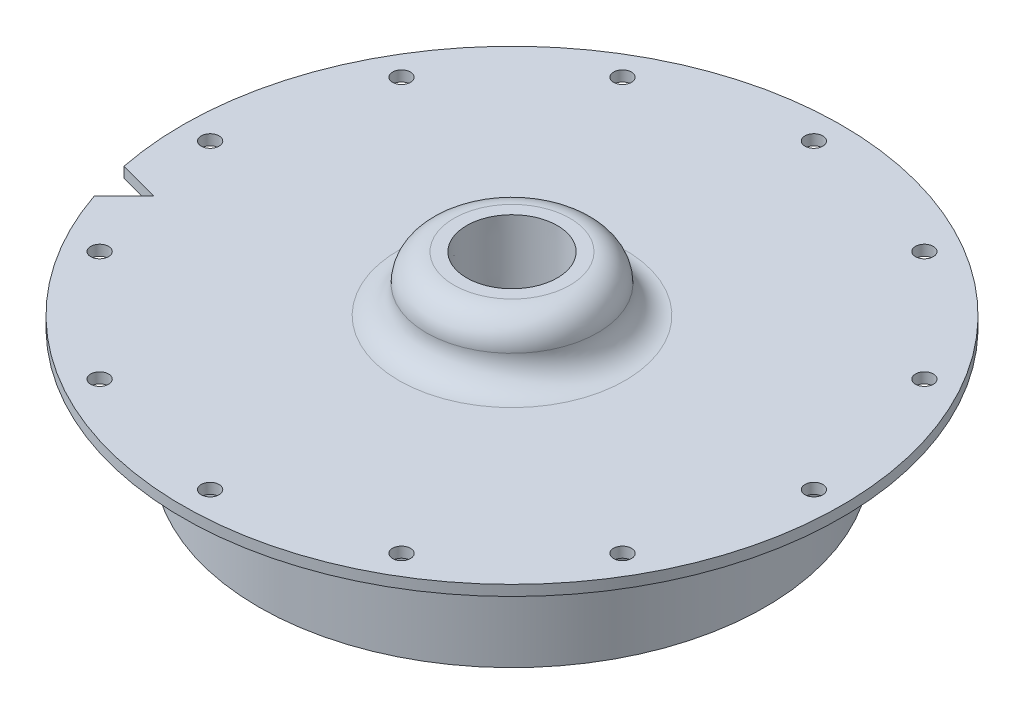
SolidWorks part; units mm, degrees
material "6063-T6"
ref_plane "Front Plane" through (0, 0, 0) normal (0, 0, 1) x (1, 0, 0)
ref_plane "Top Plane" through (0, 0, 0) normal (0, 1, 0) x (1, 0, 0)
ref_plane "Right Plane" through (0, 0, 0) normal (1, 0, 0) x (0, 0, -1)
ref_axis "Axis1" through (0, 55, 0) along (0, -1, 0)
sketch "Sketch1" plane through (0, 0, 0) normal (0, 0, 1) x (1, 0, 0)
  line L0 (-49.784, 0) -> (-39.8399, 0)
  line L1 (0, 55) -> (0, -55) construction
  line L2 (-49.784, 0) -> (-49.784, 1.5875)
  line L3 (-5.588, 9.906) -> (-8.763, 9.906)
  line L5 (-5.588, 9.906) -> (-5.588, 0)
  line L6 (-5.588, 0) -> (0, 0) construction
  line L7 (-49.784, 0) -> (-49.784, 1.5875) construction
  line L8 (-5.588, 1.5875) -> (-5.588, 0) construction
  line L9 (-38.2524, -1.5875) -> (-38.2524, -17.4625)
  line L10 (-38.2524, -17.4625) -> (-35.0774, -17.4625)
  line L11 (-35.0774, -17.4625) -> (-35.0774, -3.175)
  line L12 (-31.9024, 0) -> (-5.588, 0)
  line L13 (0, -201000) -> (0, 249000) construction
  line L14 (-49.784, 1.5875) -> (-17.0815, 1.5875)
  arc A0 (-35.0774, -3.175) -> (-31.9024, 0) centre (-31.9024, -3.175) cw
  arc A1 (-38.2524, -1.5875) -> (-39.8399, 0) centre (-39.8399, -1.5875) ccw
  arc A2 (-17.0815, 1.5875) -> (-12.9223, 5.7467) centre (-17.0815, 5.7467) ccw
  arc A3 (-8.763, 9.906) -> (-12.9223, 5.7467) centre (-8.763, 5.7467) ccw
  point P18 (-35.0774, 0)
  dimension "D4" = 3.175
  dimension "D5" = 1.5875
  dimension "D1" = 3.175
  dimension "D2" = 38.2524
  dimension "D3" = 17.4625
  dimension "D6" = 1.5875
  dimension "D7" = 3.175
  dimension "D8" = 9.906
revolve "Revolve1" add sketch "Sketch1" angle 360 about axis through (0, 55, 0) along (0, -1, 0)
ref_plane "Hole Location Plane" through (0, 3.175, 0) normal (0, 1, 0) x (1, 0, 0)
sketch "Hole Location" plane through (0, 3.175, 0) normal (0, 1, 0) x (1, 0, 0)
  line L0 (0, 0) -> (-45.6057, 0) construction
  circle A0 centre (0, 0) radius 45.6057 construction
  dimension "D1" = 91.2114
hole_wizard "#36 (0.1065) Diameter Hole1" positions "Sketch2" profile "Sketch3" hole size "#36" standard "ANSI Inch" end condition through all
sketch "Sketch2" plane through (0, 1.5875, 0) normal (0, 1, 0) x (1, 0, 0)
  point P0 (-45.6057, 0)
sketch "Sketch3" plane through (-45.6057, 1.5875, 0) normal (1, 0, 0) x (0, 0, 1)
  line L0 (0, 0) -> (0, 19.05)
  line L1 (0, 19.05) -> (1.3525, 19.05)
  line L2 (1.3525, 19.05) -> (1.3525, 0)
  line L5 (1.3525, 0) -> (0, 0)
  line L11 (0, -6.35) -> (0, 107.95) construction
  dimension "Thru Hole Dia." = 2.7051
  dimension "Thru Hole Depth" = 19.05
pattern_circular "CirPattern1" count 12 over 360 of "#36 (0.1065) Diameter Hole1"
hole_wizard "1/4 NPT Tapped Hole1" positions "Sketch4" profile "Sketch5" size "1/4" standard "ANSI Inch" end condition through all
sketch "Sketch4" plane through (0, 9.906, 0) normal (0, 1, 0) x (1, 0, 0)
  point P0 (0, 0)
sketch "Sketch5" plane through (0, 9.906, 0) normal (1, 0, 0) x (0, 0, 1)
  line L0 (0, 0) -> (0, 27.3685)
  line L1 (0, 27.3685) -> (5.5626, 27.3685)
  line L2 (-6.558, 9.906) -> (-6.8546, 0) construction
  line L3 (5.5626, 27.3685) -> (5.5626, 9.906)
  line L4 (5.5626, 9.906) -> (6.558, 9.906)
  line L5 (6.558, 9.906) -> (6.8546, 0)
  line L7 (6.8546, 0) -> (0, 0)
  line L8 (0, -6.35) -> (0, 107.95) construction
  line L11 (-5.5626, 9.906) -> (-6.558, 9.906) construction
  dimension "Thru Tap Drill Dia." = 11.1252
  dimension "Thru Tap Drill Depth" = 27.3685
  dimension "Thread Dia." = 13.7092
  dimension "Thread Angle" = 3.43
  dimension "Thread Depth" = 9.906
sketch "Sketch6" plane through (0, 1.5875, 0) normal (0, 1, 0) x (1, 0, 0)
  line L0 (0, 0) -> (-48.0877, -12.885) construction
  line L1 (0, 0) -> (-45.6057, 0) construction
  line L2 (-47.168, -15.9256) -> (-42.6779, -11.4355)
  line L3 (-42.6779, -11.4355) -> (-48.8115, -9.792)
  circle A0 centre (0, 0) radius 49.784 construction
  arc A1 (-47.168, -15.9256) -> (-48.8115, -9.792) centre (0, 0) cw
  circle M16 centre (0, 0) radius 49.784
  dimension "D1" = 15
  dimension "D2" = 60
  dimension "D3" = 6.35
extrude "Cut-Extrude1" cut sketch "Sketch6" against normal up to surface (1.5875 mm away) contours L2 L0 A1 | L0 L3 M16 region at (-45.9878, 1.5875, 13.4214) region at (-46.5373, 1.5875, 11.3707) up to face at (-39.4957, 0, -24.1554)
equation "\"D1@Hole Location\"=\"TANK DIAMETER@Cryo Tank.Assembly\"+\"GASKET SEAT THICKNESS@Cryo Tank.Assembly\"+\"LINER THICKNESS@Cryo Tank.Assembly\"+\"SHRINK FIT DELTA@Cryo Tank.Assembly\""
equation "\"D2@Sketch1\"=\"TANK DIAMETER@Cryo Tank.Assembly\"/2+\"SHRINK FIT DELTA@Cryo Tank.Assembly\""
equation "\"D3@Sketch1\"=0.5+0.125+0.0625"
